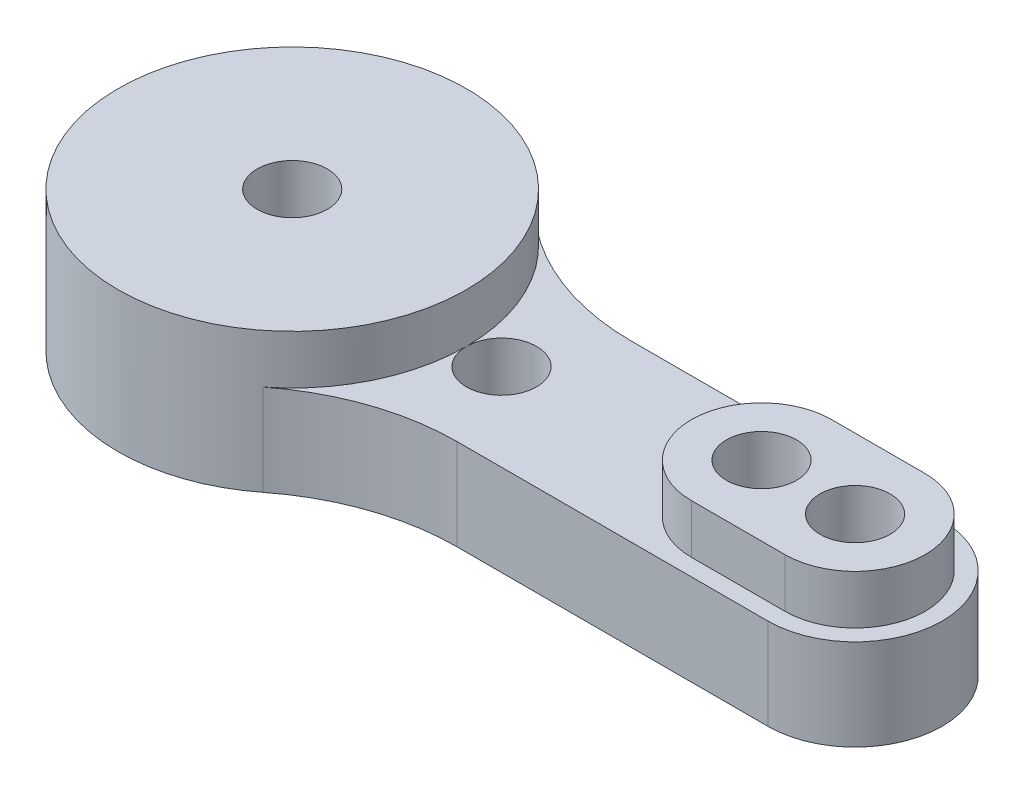
SolidWorks part; units mm, degrees
ref_plane "Front Plane" through (0, 0, 0) normal (0, 0, 1) x (1, 0, 0)
ref_plane "Top Plane" through (0, 0, 0) normal (0, 1, 0) x (1, 0, 0)
ref_plane "Right Plane" through (0, 0, 0) normal (1, 0, 0) x (0, 0, -1)
sketch "Sketch1" plane through (0, 0, 0) normal (0, 1, 0) x (1, 0, 0)
  line L0 (24.0717, 0) -> (20.0717, 0) construction
  line L5 (6.4519, 3.725) -> (24.0717, 3.725)
  line L6 (24.0717, -3) -> (20.0717, -3)
  line L7 (6.4519, -3.725) -> (24.0717, -3.725)
  line L8 (24.0717, 3) -> (20.0717, 3)
  arc A3 (6.4519, 3.725) -> (6.4519, -3.725) centre (0, 0) ccw
  arc A4 (24.0717, -3.725) -> (24.0717, 3.725) centre (24.0717, 0) ccw
  arc A5 (24.0717, -3) -> (24.0717, 3) centre (24.0717, 0) ccw
  arc A6 (20.0717, 3) -> (20.0717, -3) centre (20.0717, 0) ccw
  arc A7 (6.4519, 3.725) -> (6.4519, -3.725) centre (0, 0) cw
  circle A8 centre (20.0717, 0) radius 1.5
  circle A9 centre (24.0717, 0) radius 1.5
  circle A10 centre (0, 0) radius 1.5
  circle A11 centre (8.95, 0) radius 1.5
  point P1 (22.0717, 0)
  dimension "D4" = 6
  dimension "D5" = 4
  dimension "D6" = 3
  dimension "D1" = 14.9
  dimension "D3" = 7.45
  dimension "D7" = 3
  dimension "D8" = 3
  dimension "D9" = 3
  dimension "D2" = 24.0717
extrude "Boss-Extrude1" add sketch "Sketch1" against normal blind 3.9 contours A7 A11 L7 A4 L5 A6 L8 A5 L6 | A7 A3 A10 | L8 A6 L6 A5 A9 A8 region at (6.9926, 0, -1.8737) region at (14.7813, 0, 0) region at (22.0717, 0, 0)
extrude "Boss-Extrude2" add sketch "Sketch1<3>" along normal blind 2.1 contours L8 A6 L6 A5 A9 A8 | A7 A3 A10 region at (6.9926, 0, -1.8737) region at (22.0717, 0, 0)
sketch "Sketch1<3>" plane through (0, 0, 0) normal (0, 1, 0) x (1, 0, 0) same geometry as "Sketch1"
fillet "Fillet1" radius 10 2 edges at (6.4519, -1.95, -3.725) (6.4519, -1.95, 3.725)
